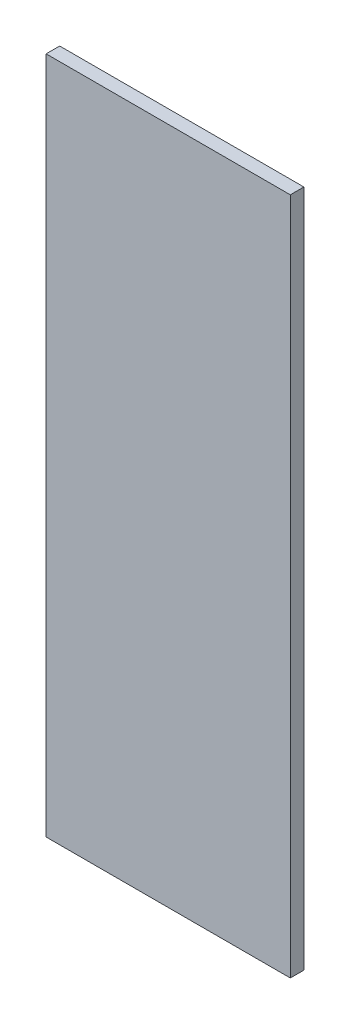
SolidWorks part; units mm, degrees
material "6061-T6 (SS)"
ref_plane "정면" through (0, 0, 0) normal (0, 0, 1) x (1, 0, 0)
ref_plane "윗면" through (0, 0, 0) normal (0, 1, 0) x (1, 0, 0)
ref_plane "우측면" through (0, 0, 0) normal (1, 0, 0) x (0, 0, -1)
sketch "스케치1" plane through (0, 0, 0) normal (0, 0, 1) x (1, 0, 0)
  line L1 (-45, 125) -> (45, 125)
  line L2 (-45, 125) -> (-45, -125)
  line L3 (-45, -125) -> (45, -125)
  line L4 (45, 125) -> (45, -125)
  line L5 (-45, 125) -> (45, -125) construction
  line L6 (-45, -125) -> (45, 125) construction
  point P0 (0, 0)
  dimension "D1" = 250
  dimension "D2" = 90
extrude "보스-돌출1" add sketch "스케치1" along normal blind 5
